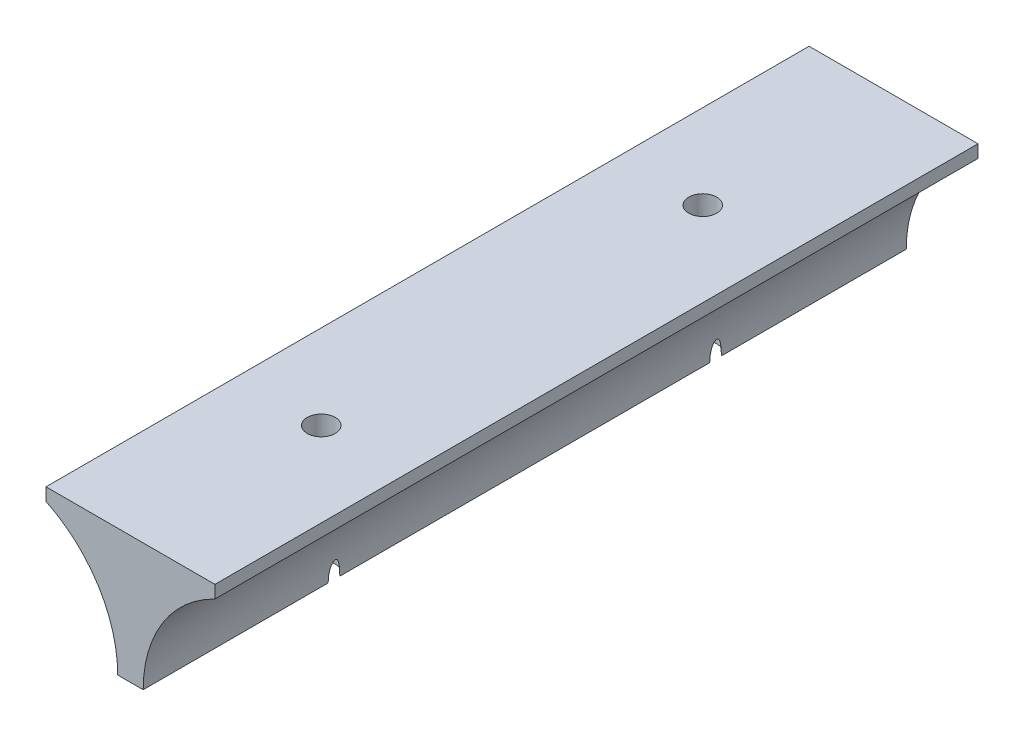
SolidWorks part; units mm, degrees
ref_plane "Front" through (0, 0, 0) normal (0, 0, 1) x (1, 0, 0)
ref_plane "Top" through (0, 0, 0) normal (0, 1, 0) x (1, 0, 0)
ref_plane "Right" through (0, 0, 0) normal (1, 0, 0) x (0, 0, -1)
sketch "Sketch1" plane through (0, 0, 0) normal (0, 0, 1) x (1, 0, 0)
  line L0 (-1, 0) -> (1, 0)
  line L1 (6.6411, 9) -> (6.6411, 10)
  line L2 (6.6411, 10) -> (-6.6411, 10)
  line L3 (-6.6411, 10) -> (-6.6411, 9)
  arc A0 (1, 0) -> (6.6411, 9) centre (11, 0) cw
  arc A1 (-1, 0) -> (-6.6411, 9) centre (-11, 0) ccw
  point P9 (0, 0)
  point P10 (0, 10)
  dimension "D1" = 10
  dimension "D2" = 10
  dimension "D3" = 2
  dimension "D4" = 1
extrude "Boss-Extrude1" add sketch "Sketch1" along normal mid plane 60
sketch "Sketch2" plane through (0, 10, 0) normal (0, 1, 0) x (1, 0, 0)
  line L0 (0, -30) -> (0, 30) construction
  line L1 (6.6411, -30) -> (-6.6411, -30) construction
  line L2 (6.6411, 30) -> (-6.6411, 30) construction
  point P6 (0, -15)
  point P7 (0, 15)
  dimension "D1" = 15
  dimension "D2" = 15
hole_wizard "Ø2.2 (2.2) Diameter Hole1" positions "3DSketch1" profile "Sketch3" hole size "Ø2.2" standard "ANSI Metric" end condition up to next
sketch3d "3DSketch1"
  point P0 (0, 10, 15)
  point P3 (0, 10, -15)
sketch "Sketch3" plane through (0, 10, 15) normal (1, 0, 0) x (0, 0, 1)
  line L0 (0, 0) -> (0, 10)
  line L1 (0, 10) -> (1.1, 10)
  line L2 (1.1, 10) -> (1.1, 0)
  line L5 (1.1, 0) -> (0, 0)
  line L11 (0, -6.35) -> (0, 107.95) construction
  dimension "Thru Hole Dia." = 2.2
  dimension "Thru Hole Depth" = 10
